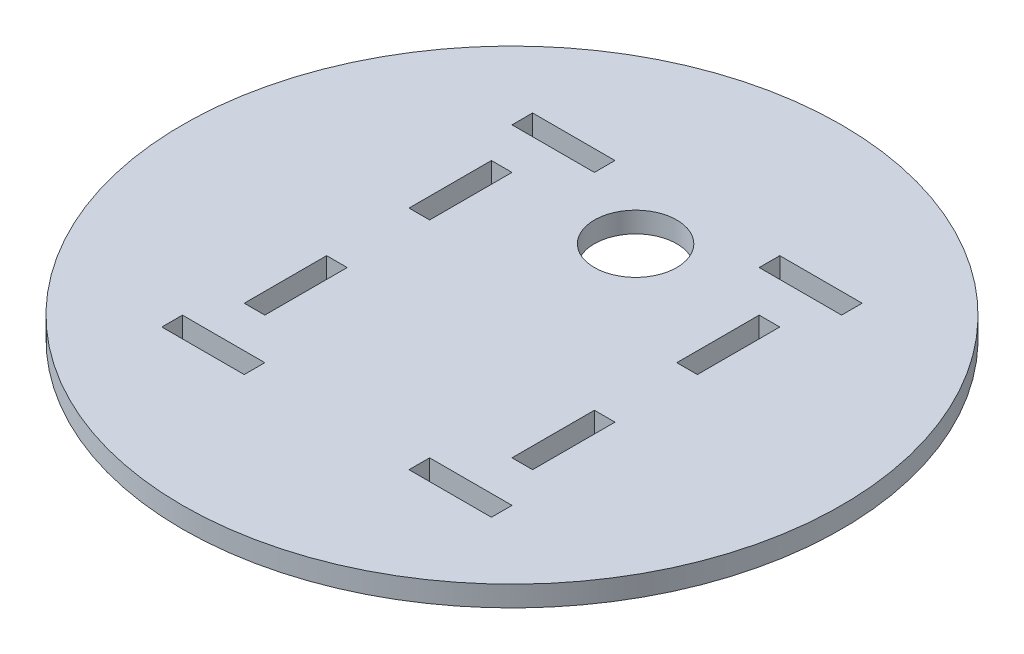
SolidWorks part; units mm, degrees
material "Pine"
ref_plane "Front Plane" through (0, 0, 0) normal (0, 0, 1) x (1, 0, 0)
ref_plane "Top Plane" through (0, 0, 0) normal (0, 1, 0) x (1, 0, 0)
ref_plane "Right Plane" through (0, 0, 0) normal (1, 0, 0) x (0, 0, -1)
sketch "Sketch1" plane through (0, 0, 0) normal (0, 1, 0) x (1, 0, 0)
  line L0 (0, 0) -> (0, 123.9148) construction
  line L1 (0, 0) -> (144.4711, 0) construction
  line L2 (-50.8, 50.8) -> (-25.4, 50.8)
  line L3 (-50.8, 50.8) -> (-50.8, 57.15)
  line L4 (-50.8, 57.15) -> (-25.4, 57.15)
  line L5 (-25.4, 50.8) -> (-25.4, 57.15)
  line L6 (25.4, 50.8) -> (25.4, 57.15)
  line L7 (50.8, 57.15) -> (25.4, 57.15)
  line L8 (50.8, 50.8) -> (50.8, 57.15)
  line L9 (50.8, 50.8) -> (25.4, 50.8)
  line L10 (-25.4, -50.8) -> (-25.4, -57.15)
  line L11 (-50.8, -50.8) -> (-25.4, -50.8)
  line L12 (-50.8, -50.8) -> (-50.8, -57.15)
  line L13 (-50.8, -57.15) -> (-25.4, -57.15)
  line L14 (50.8, -50.8) -> (50.8, -57.15)
  line L15 (50.8, -57.15) -> (25.4, -57.15)
  line L16 (25.4, -50.8) -> (25.4, -57.15)
  line L17 (50.8, -50.8) -> (25.4, -50.8)
  line L18 (38.1, -38.1) -> (44.45, -38.1)
  line L19 (38.1, 38.1) -> (44.45, 38.1)
  line L20 (38.1, 38.1) -> (38.1, 12.7)
  line L21 (38.1, 12.7) -> (44.45, 12.7)
  line L22 (44.45, 38.1) -> (44.45, 12.7)
  line L23 (38.1, -38.1) -> (38.1, -12.7)
  line L24 (38.1, -12.7) -> (44.45, -12.7)
  line L25 (44.45, -38.1) -> (44.45, -12.7)
  line L26 (-38.1, -38.1) -> (-44.45, -38.1)
  line L27 (-44.45, -38.1) -> (-44.45, -12.7)
  line L28 (-38.1, -38.1) -> (-38.1, -12.7)
  line L29 (-38.1, -12.7) -> (-44.45, -12.7)
  line L30 (-38.1, 12.7) -> (-44.45, 12.7)
  line L31 (-38.1, 38.1) -> (-38.1, 12.7)
  line L32 (-38.1, 38.1) -> (-44.45, 38.1)
  line L33 (-44.45, 38.1) -> (-44.45, 12.7)
  circle A0 centre (0, 0) radius 101.6
  circle A1 centre (0, 38.1) radius 12.7
  dimension "D1" = 203.2
  dimension "D10" = 25.4
  dimension "D2" = 25.4
  dimension "D3" = 25.4
  dimension "D4" = 6.35
  dimension "D5" = 50.8
  dimension "D6" = 6.35
  dimension "D7" = 25.4
  dimension "D8" = 12.7
  dimension "D9" = 38.1
  dimension "D11" = 38.1
extrude "Boss-Extrude1" add sketch "Sketch1" along normal blind 6.35
